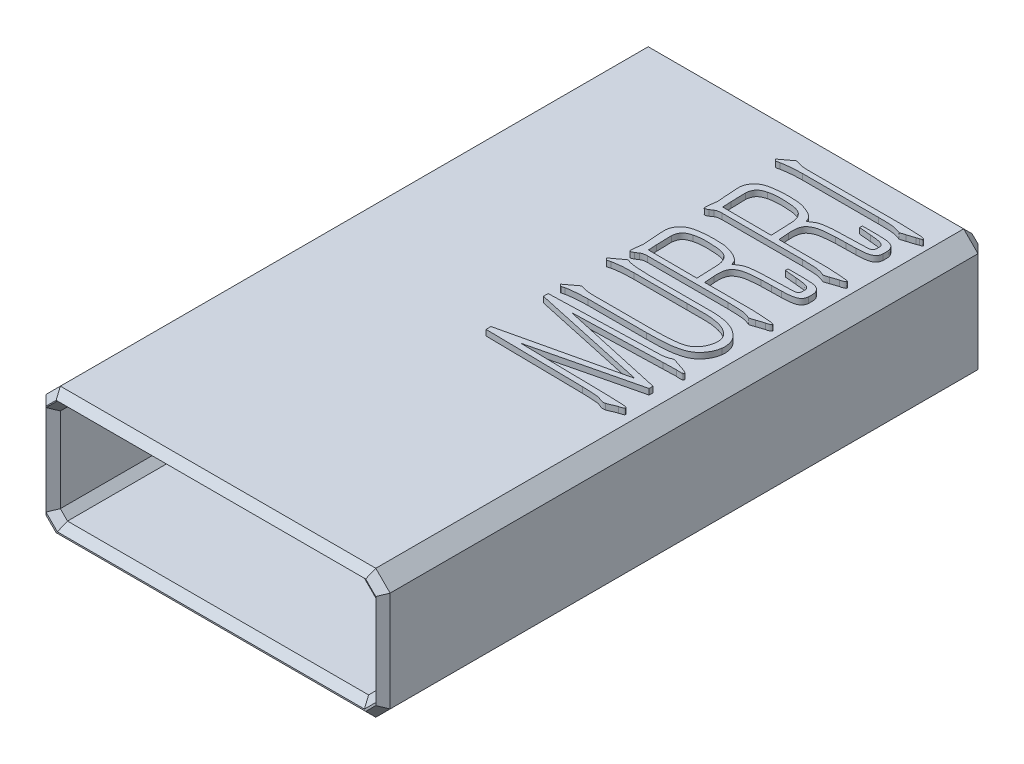
SolidWorks part; units mm, degrees
ref_plane "Front Plane" through (0, 0, 0) normal (0, 0, 1) x (1, 0, 0)
ref_plane "Top Plane" through (0, 0, 0) normal (0, 1, 0) x (1, 0, 0)
ref_plane "Right Plane" through (0, 0, 0) normal (1, 0, 0) x (0, 0, -1)
sketch "Sketch1" plane through (0, 0, 0) normal (0, 0, 1) x (1, 0, 0)
  line L1 (0, 4.5) -> (12, 4.5)
  line L2 (0, 4.5) -> (0, 0)
  line L3 (0, 0) -> (12, 0)
  line L4 (12, 4.5) -> (12, 0)
  line L5 (0.5, 4) -> (11.5, 4)
  line L6 (0.5, 4) -> (0.5, 0.55)
  line L7 (0.5, 0.55) -> (11.5, 0.55)
  line L8 (11.5, 4) -> (11.5, 0.55)
  point P8 (0, 0)
  dimension "D1" = 12
  dimension "D2" = 4.5
  dimension "D3" = 0.5
  dimension "D4" = 0.5
  dimension "D5" = 0.55
  dimension "D6" = 0.5
extrude "Boss-Extrude1" add sketch "Sketch1" along normal blind 21.25
sketch "Sketch2" plane through (0, 0, 0) normal (0, 0, 1) x (1, 0, 0)
  line L0 (0, 0) -> (12, 0) construction
  line L1 (12, 0) -> (12, 4.5) construction
  line L2 (12, 4.5) -> (0, 4.5) construction
  line L3 (0, 4.5) -> (0, 0) construction
  line L4 (0, 0) -> (12, 0)
  line L5 (12, 0) -> (12, 4.5)
  line L6 (12, 4.5) -> (0, 4.5)
  line L7 (0, 4.5) -> (0, 0)
extrude "Boss-Extrude2" add sketch "Sketch2" along normal blind 1
chamfer "Chamfer1" distance 0.25 angle 45 4 edges at (11.5, 0.55, 11.125) (11.5, 4, 11.125) (0.5, 0.55, 11.125) (0.5, 4, 11.125)
chamfer "Chamfer2" distance 0.5 angle 45 4 edges at (12, 0, 10.625) (12, 4.5, 10.625) (0, 0, 10.625) (0, 4.5, 10.625)
chamfer "Chamfer3" distance 0.5 angle 45 8 edges at (12, 2.25, 0) (6, 0, 0) (0, 2.25, 0) (6, 4.5, 0) (11.75, 4.25, 0) (11.75, 0.25, 0) (0.25, 0.25, 0) (0.25, 4.25, 0)
chamfer "Chamfer4" distance 0.25 angle 45 8 edges at (11.75, 4.25, 21.25) (12, 2.25, 21.25) (11.75, 0.25, 21.25) (6, 0, 21.25) (0.25, 0.25, 21.25) (0, 2.25, 21.25) (0.25, 4.25, 21.25) (6, 4.5, 21.25)
chamfer "Chamfer5" distance 0.25 angle 45 8 edges at (11.375, 0.675, 21.25) (11.5, 2.275, 21.25) (11.375, 3.875, 21.25) (6, 0.55, 21.25) (0.625, 0.675, 21.25) (0.5, 2.275, 21.25) (0.625, 3.875, 21.25) (6, 4, 21.25)
sketch "Sketch3" plane through (0, 4.5, 0) normal (0, 1, 0) x (1, 0, 0)
  line L0 (11.5, -13.1661) -> (11.5, -0.5) construction
  line L2 (11.5, -0.5) -> (0.5, -0.5) construction
  text T0 "MURRI" font "HYSWLongFangSong" height 5
  point P3 (3.8844, -11.8917)
  point P4 (11.5, -0.5)
extrude "Boss-Extrude3" add sketch "Sketch3" along normal blind 0.2
